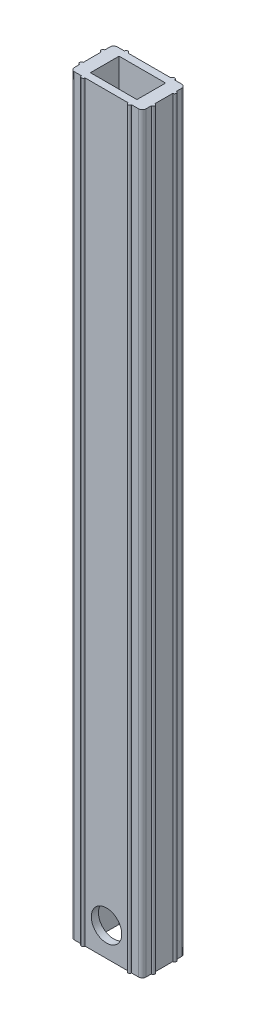
SolidWorks part; units mm, degrees
ref_plane "Спереди" through (0, 0, 0) normal (0, 0, 1) x (1, 0, 0)
ref_plane "Сверху" through (0, 0, 0) normal (0, 1, 0) x (1, 0, 0)
ref_plane "Справа" through (0, 0, 0) normal (1, 0, 0) x (0, 0, -1)
sketch "Эскиз1" plane through (0, 0, 0) normal (0, 1, 0) x (1, 0, 0)
  line L0 (-10, 3.5) -> (-10, 5)
  line L1 (9, -6) -> (7, -6)
  line L2 (10, -5) -> (10, -3.5)
  line L3 (9, 6) -> (7, 6)
  line L4 (-10, -5) -> (-10, -3.5)
  line L5 (10, -6) -> (-10, 6) construction
  line L6 (10, 6) -> (-10, -6) construction
  line L7 (6.5, 4) -> (-6.5, 4)
  line L8 (6.5, 4) -> (6.5, -4)
  line L9 (6.5, -4) -> (-6.5, -4)
  line L10 (-6.5, 4) -> (-6.5, -4)
  line L11 (6.5, 4) -> (-6.5, -4) construction
  line L12 (6.5, -4) -> (-6.5, 4) construction
  line L13 (-10, -2.5) -> (-10, 2.5)
  line L14 (-7, 6) -> (-9, 6)
  line L15 (6, 6) -> (-6, 6)
  line L16 (10, 3.5) -> (10, 5)
  line L17 (10, -2.5) -> (10, 2.5)
  line L18 (6, -6) -> (-6, -6)
  line L19 (-7, -6) -> (-9, -6)
  arc A0 (9, 6) -> (10, 5) centre (9, 5) cw
  arc A1 (9, -6) -> (10, -5) centre (9, -5) ccw
  arc A2 (-9, -6) -> (-10, -5) centre (-9, -5) cw
  arc A3 (-10, 5) -> (-9, 6) centre (-9, 5) cw
  arc A4 (10, 2.5) -> (10, 3.5) centre (10, 3) ccw
  arc A5 (10, -3.5) -> (10, -2.5) centre (10, -3) ccw
  arc A6 (-10, 3.5) -> (-10, 2.5) centre (-10, 3) ccw
  arc A7 (-10, -2.5) -> (-10, -3.5) centre (-10, -3) ccw
  arc A8 (-6, 6) -> (-7, 6) centre (-6.5, 6) ccw
  arc A9 (7, 6) -> (6, 6) centre (6.5, 6) ccw
  arc A10 (-7, -6) -> (-6, -6) centre (-6.5, -6) ccw
  arc A11 (6, -6) -> (7, -6) centre (6.5, -6) ccw
  point P0 (0, 0)
  point P5 (0, 0)
  dimension "D5" = 1
  dimension "D6" = 3
  dimension "D1" = 20
  dimension "D2" = 12
  dimension "D3" = 13
  dimension "D4" = 8
  dimension "D7" = 3
extrude "Бобышка-Вытянуть1" add sketch "Эскиз1" along normal blind 105 and the other way blind 105
sketch "Эскиз2" plane through (0, 0, 6) normal (0, 0, 1) x (1, 0, 0)
  line L0 (-6, -105) -> (6, -105) construction
  circle A0 centre (0, -97) radius 4.25
  dimension "D1" = 8
  dimension "D2" = 8.5
extrude "Вырез-Вытянуть1" cut sketch "Эскиз2" against normal through all and the other way through all
sketch "Эскиз3" plane through (0, 0, 0) normal (1, 0, 0) x (0, 0, -1)
  circle A0 centre (0, -11) radius 3
  circle A1 centre (0, 11) radius 3
  circle A2 centre (0, 33) radius 3
  circle A3 centre (0, 55) radius 3
  circle A4 centre (0, 77) radius 3
  circle A5 centre (0, -33) radius 3
  circle A6 centre (0, -55) radius 3
  circle A7 centre (0, -77) radius 3
  dimension "D1" = 6
  dimension "D2" = 11
  dimension "D3" = 22
  dimension "D4" = 22
  dimension "D5" = 22
  dimension "D6" = 22
  dimension "D7" = 22
  dimension "D8" = 22
  dimension "D9" = 22
extrude "Вырез-Вытянуть2" cut sketch "Эскиз3" against normal through all
